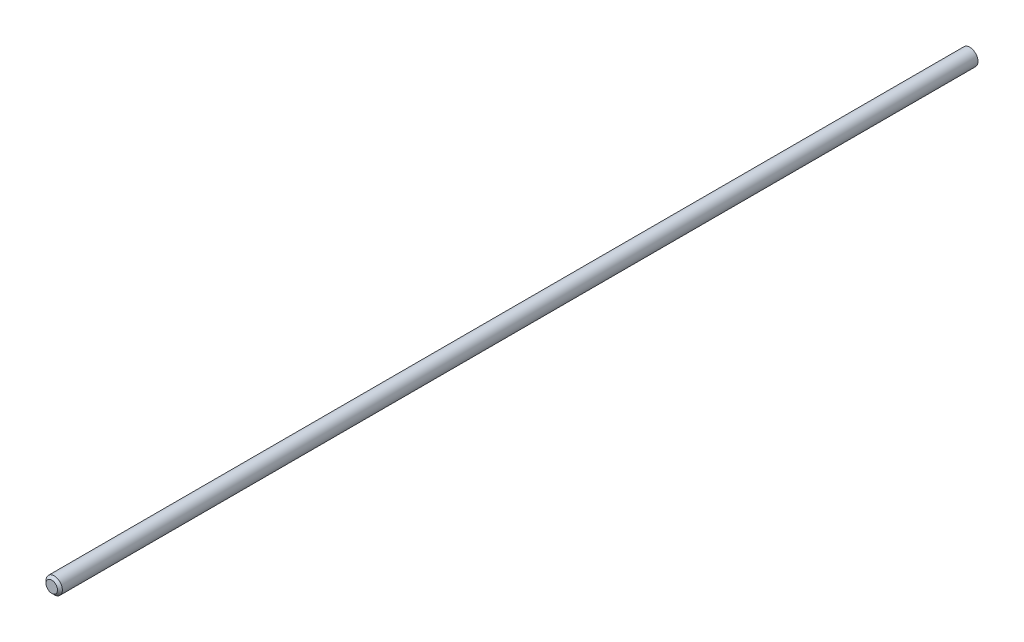
SolidWorks part; units mm, degrees
ref_plane "Front Plane" through (0, 0, 0) normal (0, 0, 1) x (1, 0, 0)
ref_plane "Top Plane" through (0, 0, 0) normal (0, 1, 0) x (1, 0, 0)
ref_plane "Right Plane" through (0, 0, 0) normal (1, 0, 0) x (0, 0, -1)
sketch "Sketch1" plane through (0, 0, 0) normal (1, 0, 0) x (0, 0, -1)
  line L1 (-304.8, 3.175) -> (304.8, 3.175)
  line L2 (-304.8, 3.175) -> (-304.8, 0)
  line L3 (-304.8, 0) -> (304.8, 0) construction
  line L4 (304.8, 3.175) -> (304.8, 0)
  point P4 (0, 0)
  point P5 (-303.53, 3.175)
  point P7 (-214.63, 3.175)
  point P8 (301.625, 3.175)
  point P9 (301.625, -3.175)
  dimension "Thread Diameter" = 6.35
  dimension "Length" = 609.6
  dimension "Thread Pitch" = 1.27
  dimension "Segment Length" = 90.17
  dimension "D1" = 3.175
sketch "Sketch2" plane through (0, 0, 0) normal (1, 0, 0) x (0, 0, -1)
  line L1 (-304.8, 0) -> (304.8, 0)
  line L2 (-304.8, 0) -> (-304.8, 3.175)
  line L3 (-304.8, 3.175) -> (304.8, 3.175)
  line L4 (304.8, 0) -> (304.8, 3.175)
revolve "Revolve1" add sketch "Sketch2" angle 360 about L1
chamfer "Chamfer1" distance 0.9525 angle 45 2 edges at (3.175, 0, -304.8) (3.175, 0, 304.8)
sketch "Drawing Reference 1" plane through (0, 0, 0) normal (1, 0, 0) x (0, 0, -1)
  line L0 (-304.8, 3.175) -> (304.8, 3.175) construction
  line L1 (-304.8, 3.175) -> (-304.8, 0) construction
  line L2 (304.8, 3.175) -> (304.8, 0) construction
  point P0 (-300.0375, 3.175)
  point P1 (300.0375, 3.175)
  dimension "D1" = 4.7625
  dimension "D2" = 4.7625
sketch "Sketch3" [suppressed] plane through (0, 0, -304.8) normal (0, 0, -1) x (-1, 0, 0)
  circle A0 centre (0, 0) radius 3.175 construction
  circle A1 centre (0, 0) radius 3.175
curve "Helix/Spiral1" [suppressed] pitch 1.27 height 91.44 turns 72
sketch "Sketch4" [suppressed] plane through (0, 0, 0) normal (1, 0, 0) x (0, 0, -1)
  line L0 (304.7206, 3.3125) -> (305.3556, 2.2126) construction
  line L1 (305.3556, 2.2126) -> (305.9906, 3.3125) construction
  line L2 (305.9906, 3.3125) -> (304.7206, 3.3125) construction
  line L3 (304.7603, 3.2437) -> (305.9509, 3.2437)
  line L4 (305.9509, 3.2437) -> (305.435, 2.3501)
  line L5 (305.435, 2.3501) -> (305.2763, 2.3501)
  line L6 (305.2763, 2.3501) -> (304.7603, 3.2437)
  line L7 (305.3556, 2.3501) -> (305.3556, 2.2126) construction
  line L8 (304.8, 3.175) -> (305.9113, 3.175) construction
  line L9 (305.3556, 3.3125) -> (305.3556, 3.175) construction
  point P12 (305.3556, 3.2437)
  dimension "D1" = 1.27
  dimension "D2" = 0.1588
sweep "Cut-Sweep1" [suppressed] cut profiles "Sketch4" path "Helix/Spiral1"
pattern_linear "LPattern1" [suppressed] of bodies 105
sketch "Sketch5" plane through (0, 0, 0) normal (1, 0, 0) x (0, 0, -1)
  line L0 (-304.8, 2.2225) -> (-304.8, -2.2225) construction
  line L1 (304.8, 25.4) -> (50.8, 25.4)
  line L2 (304.8, 25.4) -> (304.8, -25.4)
  line L3 (304.8, -25.4) -> (50.8, -25.4)
  line L4 (50.8, 25.4) -> (50.8, -25.4)
  line L5 (304.8, -2.2225) -> (304.8, 2.2225) construction
  dimension "D1" = 355.6
  dimension "D2" = 25.4
  dimension "D3" = 25.4
extrude "Cut-Extrude1" cut sketch "Sketch5" against normal through all both and the other way through all
equation "\"D1@Chamfer1\"=0.75*\"Thread Pitch@Sketch1\""
equation "\"Segment Length@Sketch1\"=\"Thread Pitch@Sketch1\"*71"
equation "\"D4@Helix/Spiral1\"=\"Thread Pitch@Sketch1\""
equation "\"D5@Helix/Spiral1\"=(\"Segment Length@Sketch1\"/\"Thread Pitch@Sketch1\")+1"
equation "\"D2@Sketch4\"=\"D1@Sketch4\"/8"
equation "\"D1@Sketch4\"=\"Thread Pitch@Sketch1\""
equation "\"D3@LPattern1\"=\"Segment Length@Sketch1\""
equation "\"D1@Drawing Reference 1\"=\"Thread Diameter@Sketch1\"*0.75"
equation "\"D2@Drawing Reference 1\" = \"D1@Drawing Reference 1\""
equation "\"D1@Sketch1\"=2.5*\"Thread Pitch@Sketch1\""
